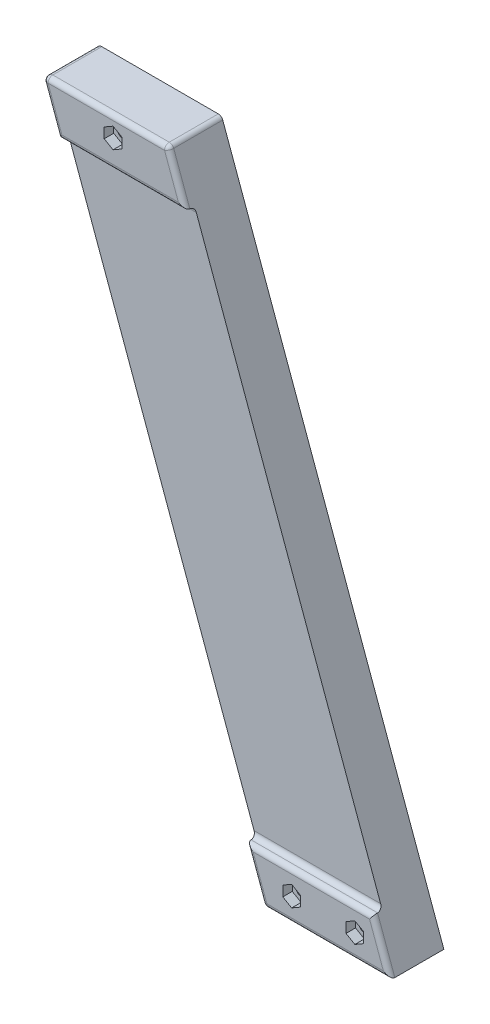
SolidWorks part; units mm, degrees
note: The reader was unsure of these and kept them because the rebuilt part matched: shared geometry of "Sketch2<17>", "Sketch2<18>".
ref_plane "Front Plane" through (0, 0, 0) normal (0, 0, 1) x (1, 0, 0)
ref_plane "Top Plane" through (0, 0, 0) normal (0, 1, 0) x (1, 0, 0)
ref_plane "Right Plane" through (0, 0, 0) normal (1, 0, 0) x (0, 0, -1)
sketch "Sketch3" plane through (0, 0, 0) normal (0, 0, 1) x (1, 0, 0)
  line L1 (-127.0377, 374.6099) -> (92.9623, 374.6099)
  line L2 (-127.0377, 374.6099) -> (-127.0377, 154.6099)
  line L3 (-127.0377, 154.6099) -> (92.9623, 154.6099)
  line L4 (92.9623, 374.6099) -> (92.9623, 154.6099)
  dimension "D1" = 220
  dimension "D2" = 220
sketch "Sketch1" plane through (0, 0, 0) normal (0, 0, 1) x (1, 0, 0)
  line L0 (5, 40.95) -> (25, 40.95)
  line L1 (0, 0) -> (30, 0)
  line L2 (0, 0) -> (0, 34.5)
  line L3 (0, 34.5) -> (30, 34.5)
  line L4 (30, 0) -> (30, 34.5)
  line L5 (0, 0) -> (30, 0)
  line L6 (0, 0) -> (0, -4)
  line L7 (0, -4) -> (30, -4)
  line L8 (30, 0) -> (30, -4)
  line L9 (0, 34.5) -> (30, 34.5)
  line L10 (0, 34.5) -> (0, 44.5)
  line L11 (0, 44.5) -> (30, 44.5)
  line L12 (30, 34.5) -> (30, 44.5)
  line L14 (8.2332, 40.95) -> (6.6166, 43.75)
  line L15 (6.6166, 43.75) -> (3.3834, 43.75)
  line L16 (3.3834, 43.75) -> (1.7668, 40.95)
  line L17 (1.7668, 40.95) -> (3.3834, 38.15)
  line L18 (3.3834, 38.15) -> (6.6166, 38.15)
  line L19 (6.6166, 38.15) -> (8.2332, 40.95)
  line L20 (21.7668, 40.95) -> (23.3834, 38.15)
  line L21 (23.3834, 38.15) -> (26.6166, 38.15)
  line L22 (26.6166, 38.15) -> (28.2332, 40.95)
  line L23 (28.2332, 40.95) -> (26.6166, 43.75)
  line L24 (26.6166, 43.75) -> (23.3834, 43.75)
  line L25 (23.3834, 43.75) -> (21.7668, 40.95)
  circle A0 centre (15, 8) radius 6.5
  circle A1 centre (5, 40.95) radius 1.55
  circle A2 centre (25, 40.95) radius 1.55
  circle A3 centre (5, 40.95) radius 2.8 construction
  circle A4 centre (25, 40.95) radius 2.8 construction
  point P10 (15, 0)
  point P16 (5, 42.5)
  point P17 (5, 39.4)
  point P18 (15, 40.95)
  point P19 (15, 34.5)
  dimension "D4" = 13
  dimension "D7" = 3.1
  dimension "D10" = 5.6
  dimension "D1" = 30
  dimension "D2" = 34.5
  dimension "D3" = 4
  dimension "D5" = 8
  dimension "D6" = 20
  dimension "D8" = 4.9
  dimension "D9" = 2
sketch "Sketch2" plane through (0, 0, 0) normal (0, 0, 1) x (1, 0, 0)
  line L0 (0, 34.5) -> (-53.8676, 182.5)
  line L1 (-53.8676, 182.5) -> (-53.8676, 34.5)
  line L2 (-53.8676, 34.5) -> (0, 34.5)
  line L3 (30, 44.5) -> (-82.8834, 354.6447)
  line L4 (-82.8834, 354.6447) -> (-119.7157, 354.6447)
  line L5 (-119.7157, 354.6447) -> (-3.1925, 34.5)
  line L6 (-53.8676, 182.5) -> (-115.4312, 351.6447)
  line L7 (-55.9682, 179.5) -> (-19.136, 179.5)
  line L8 (-50.5087, 164.5) -> (-13.6764, 164.5)
  line L9 (-44.8223, 172) -> (-24.8223, 172)
  line L10 (-24.8223, 168.7668) -> (-22.0223, 170.3834)
  line L11 (-22.0223, 170.3834) -> (-22.0223, 173.6166)
  line L12 (-22.0223, 173.6166) -> (-24.8223, 175.2332)
  line L13 (-24.8223, 175.2332) -> (-27.6223, 173.6166)
  line L14 (-27.6223, 173.6166) -> (-27.6223, 170.3834)
  line L15 (-27.6223, 170.3834) -> (-24.8223, 168.7668)
  line L16 (-44.8223, 168.7668) -> (-42.0223, 170.3834)
  line L17 (-42.0223, 170.3834) -> (-42.0223, 173.6166)
  line L18 (-42.0223, 173.6166) -> (-44.8223, 175.2332)
  line L19 (-44.8223, 175.2332) -> (-47.6223, 173.6166)
  line L20 (-47.6223, 173.6166) -> (-47.6223, 170.3834)
  line L21 (-47.6223, 170.3834) -> (-44.8223, 168.7668)
  line L22 (-37.5521, 179.5) -> (-32.0925, 164.5)
  line L23 (-22.3285, 179.5) -> (-16.869, 164.5)
  line L24 (-52.7757, 179.5) -> (-47.3161, 164.5)
  line L25 (-44.1637, 179.5) -> (4.9723, 44.5)
  line L26 (0, 44.5) -> (30, 44.5) construction
  line L27 (-30.9405, 179.5) -> (18.1955, 44.5)
  line L28 (4.9723, 44.5) -> (18.1955, 44.5)
  line L29 (-44.1637, 179.5) -> (-30.9405, 179.5)
  line L30 (18.1955, 44.5) -> (30, 44.5)
  line L31 (4.9723, 44.5) -> (0, 44.5)
  line L32 (0, 44.5) -> (0, 34.5)
  line L33 (-3.1925, 34.5) -> (0, 25.7286)
  line L34 (0, 0) -> (0, 34.5) construction
  line L35 (0, 25.7286) -> (0, 34.5)
  line L36 (-50.5087, 164.5) -> (-53.7012, 164.5)
  line L37 (-53.7012, 164.5) -> (-124.0001, 357.6447)
  line L41 (-82.8834, 354.6447) -> (-83.9753, 357.6447)
  line L42 (-83.9753, 357.6447) -> (-124.0001, 357.6447)
  line L43 (-22.3285, 179.5) -> (-86.076, 354.6447)
  line L44 (-101.2995, 354.6447) -> (-104.0995, 353.0281)
  line L45 (-104.0995, 353.0281) -> (-104.0995, 349.7949)
  line L46 (-104.0995, 349.7949) -> (-101.2995, 348.1783)
  line L47 (-101.2995, 348.1783) -> (-98.4995, 349.7949)
  line L48 (-98.4995, 349.7949) -> (-98.4995, 353.0281)
  line L49 (-98.4995, 353.0281) -> (-101.2995, 354.6447)
  line L50 (-98.4995, 353.0281) -> (-104.0995, 353.0281)
  line L51 (-98.4995, 353.0281) -> (-98.4995, 357.6447)
  line L52 (-98.4995, 357.6447) -> (-104.0995, 357.6447)
  line L53 (-104.0995, 353.0281) -> (-104.0995, 357.6447)
  line L54 (-52.0477, 177.5) -> (-55.2403, 177.5)
  circle A0 centre (-53.8676, 182.5) radius 2.5
  circle A1 centre (-66.1803, 216.3289) radius 2.5
  circle A2 centre (-78.493, 250.1579) radius 2.5
  circle A3 centre (-90.8058, 283.9868) radius 2.5
  circle A4 centre (-103.1185, 317.8157) radius 2.5
  circle A5 centre (-115.4312, 351.6447) radius 2.5
  circle A6 centre (-115.4312, 351.6447) radius 3
  circle A7 centre (-53.8676, 182.5) radius 3
  circle A8 centre (-24.8223, 172) radius 2.8 construction
  circle A9 centre (-44.8223, 172) radius 2.8 construction
  circle A10 centre (-44.8223, 172) radius 1.6
  circle A11 centre (-24.8223, 172) radius 1.6
  circle A12 centre (-101.2995, 351.4115) radius 2.8 construction
  circle A13 centre (-101.2995, 351.4115) radius 1.6
  point P44 (-34.8223, 172)
  point P45 (-34.8223, 172)
  point P78 (-101.2995, 354.6447)
  dimension "D3" = 5
  dimension "D5" = 6
  dimension "D8" = 5.6
  dimension "D10" = 3.2
  dimension "D16" = 5.6
  dimension "D18" = 3.2
  dimension "D1" = 148
  dimension "D2" = 70
  dimension "D6" = 180
  dimension "D7" = 15
  dimension "D9" = 20
  dimension "D11" = 3
  dimension "D12" = 3
  dimension "D13" = 12.4258
  dimension "D14" = 3
  dimension "D15" = 3
  dimension "D17" = 2
  dimension "D4" = 6
extrude "Boss-Extrude1" add sketch "Sketch2" against normal blind 17 contours L7 L23 L8 L3 | L43 L7 L3 L4 | L51 L4 L41 L42 | L53 L4 L51 L42 | L4 L53 L42 L37 L1 L5 | L37 L36 L5 L1 | L5 L8 L0 L7 L1 | L48 L50 L45 L46 L47 A13 | L50 L49 L44 | L49 L51 L4 | L53 L44 L4 | L1 L54 L5
extrude "Boss-Extrude2" add sketch "Sketch2<17>" against normal blind 6
sketch "Sketch2<17>" plane through (0, 0, 0) normal (0, 0, 1) x (1, 0, 0) same geometry as "Sketch2"
extrude "Cut-Extrude1" cut sketch "Sketch2<18>" against normal blind 3
sketch "Sketch2<18>" plane through (0, 0, 0) normal (0, 0, 1) x (1, 0, 0) same geometry as "Sketch2"
sketch "Sketch5" plane through (0, 0, 0) normal (0, 0, 1) x (1, 0, 0)
  line L0 (-118.5406, 342.6447) -> (-78.5158, 342.6447)
  line L1 (-53.7012, 164.5) -> (-124.0001, 357.6447) construction
  line L2 (30, 44.5) -> (-82.8834, 354.6447) construction
  line L3 (-118.5406, 342.6447) -> (-59.1608, 179.5)
  line L4 (-59.1608, 179.5) -> (-19.136, 179.5)
  line L5 (-19.136, 179.5) -> (-78.5158, 342.6447)
  line L6 (-83.9753, 357.6447) -> (-124.0001, 357.6447) construction
  line L8 (-55.9682, 179.5) -> (-19.136, 179.5) construction
  dimension "D1" = 15
extrude "Cut-Extrude2" cut sketch "Sketch5" against normal offset from surface (3 mm away) 3 up to face at (-80.342, 286.3952, -6)
fillet "Fillet1" radius 1.5 17 edges at (-121.2703, 350.1447, 0) (-81.2456, 350.1447, 0) (-59.1608, 179.5, -1.5) (-118.5406, 342.6447, -1.5) (-78.5158, 342.6447, -1.5) (-19.136, 179.5, -1.5) (-39.1484, 179.5, 0) (-98.5282, 342.6447, 0) (-98.5282, 342.6447, -3) (-39.1484, 179.5, -3) (-56.431, 172, 0) (-103.9877, 357.6447, 0) (-16.4062, 172, 0) (-33.6888, 164.5, 0) (-53.7012, 164.5, -8.5) (-124.0001, 357.6447, -8.5) (-83.9753, 357.6447, -8.5)
chamfer "Chamfer2" distance 2 angle 45 1 edges at (-55.2403, 177.5, -11.5)
chamfer "Chamfer3" distance 1 angle 45 2 edges at (-87.82, 267.012, -17) (-111.9076, 354.6447, -17)
